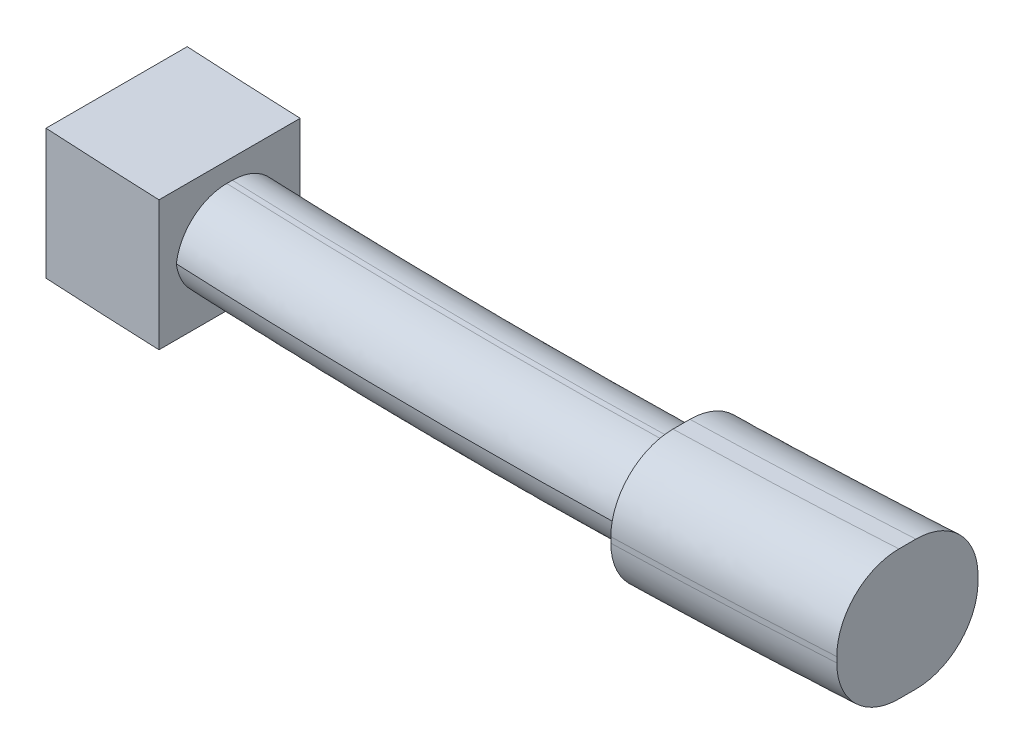
SolidWorks part; units mm, degrees
ref_plane "Front Plane" through (0, 0, 0) normal (0, 0, 1) x (1, 0, 0)
ref_plane "Top Plane" through (0, 0, 0) normal (0, 1, 0) x (1, 0, 0)
ref_plane "Right Plane" through (0, 0, 0) normal (1, 0, 0) x (0, 0, -1)
sketch "Sketch1" plane through (0, 0, 0) normal (0, 1, 0) x (1, 0, 0)
  line L1 (70, -12.5) -> (-70, -12.5)
  line L2 (70, -12.5) -> (70, 12.5)
  line L3 (70, 12.5) -> (-70, 12.5)
  line L4 (-70, -12.5) -> (-70, 12.5)
  line L5 (70, -12.5) -> (-70, 12.5) construction
  line L6 (70, 12.5) -> (-70, -12.5) construction
  point P0 (0, 0)
  point P5 (-70, 0)
  dimension "D1" = 140
  dimension "D2" = 25
extrude "Boss-Extrude1" add sketch "Sketch1" along normal blind 25
sketch "Sketch2" plane through (0, 0, 12.5) normal (0, 0, 1) x (1, 0, 0)
  line L0 (-70, 22.8376) -> (70, 22.8376)
  line L1 (-70, 25) -> (-70, 0) construction
  line L2 (70, 25) -> (70, 0) construction
  spline S0 degree 2 poles (-70, 12.5) (0, 10.0003) (70, 12.5) knots 0 0 0 1 1 1
  point P8 (-500000, 60752.5992)
sketch "Sketch3" plane through (-70, 0, 0) normal (-1, 0, 0) x (0, 0, 1)
  line L0 (12.5, 25) -> (-12.5, 0)
  line L1 (-12.5, 25) -> (12.5, 0)
  circle A0 centre (0, 12.5) radius 12.5
  point P10 (14.9425, 56.9827)
sketch "Sketch4" plane through (70, 0, 0) normal (1, 0, 0) x (0, 0, -1)
  line L0 (12.5, 25) -> (-12.5, 0)
  line L1 (-12.5, 25) -> (12.5, 0)
  circle A0 centre (0, 12.5) radius 12.4007
  point P10 (-7.4057, 0.9787)
sketch "Sketch5" plane through (0, 0, 12.5) normal (0, 0, 1) x (1, 0, 0)
  line L0 (30, 23.3673) -> (30, 19.8673)
  line L1 (-70, 25) -> (70, 25)
  line L2 (-50, 24.0204) -> (-50, 20.5204)
  line L3 (-70, 25) -> (70, 25) construction
  line L4 (-50, 20.5204) -> (-50, 1.0204)
  line L5 (30, 25) -> (-50, 25)
  line L6 (0, 11.2502) -> (0, 25)
  line L7 (-70, 21.5) -> (-50, 21.5)
  line L8 (0, 11.2502) -> (0, 14.7502)
  line L9 (-70, 25) -> (-70, 21.5)
  line L10 (-50, 1.0204) -> (-50, 4.813)
  line L11 (-70, 0) -> (-70, 2)
  line L12 (-70, 2) -> (-70, 0)
  line L13 (-70, 0) -> (70, 0)
  line L14 (70, 0) -> (70, 2)
  line L15 (0, 23) -> (0, 19.5)
  line L16 (30, 23.3673) -> (30, 0.3673)
  line L17 (30, 0.3673) -> (30, 3.8673)
  line L18 (0, 0) -> (0, 3.5)
  spline S0 degree 2 poles (-70, 25) (0, 21) (70, 25) knots 0 0 0 1 1 1
  spline S1 degree 2 poles (-70, 2) (0, -2) (70, 2) knots 0 0 0 1 1 1
  spline S2 degree 2 poles (-50, 20.5204) (-10.0053, 18.8878) (30, 19.8673) knots 0 0 0 1 1 1
  spline S3 degree 2 poles (-50, 4.813) (-10.0108, 2.8) (30, 3.8673) knots 0 0 0 1 1 1
  point P34 (0, 0)
  line M4 (-70, 0) -> (70, 0)
  line M5 (70, 0) -> (70, 25)
  line M6 (70, 25) -> (-70, 25)
  line M7 (-70, 25) -> (-70, 0)
  dimension "D1" = 3.5
  dimension "D2" = 3.5
  dimension "D3" = 3.5
  dimension "D4" = 3.5
  dimension "D5" = 3.5
  dimension "D6" = 3.5
  dimension "D7" = 3.5
  dimension "D8" = 3.5
extrude "Cut-Extrude1" cut sketch "Sketch5" against normal blind 25 contours S0 L6 L5 M6 | L6 S0 L1 M6 | L6 S2 L0 S0 | L2 S2 L6 S0 | S3 L4 S1 L18 | S3 L18 S1 L16 | S1 L13 M5 | S1 M7 M4 region at (15, 21.3725, 12.5) region at (26.25, 24.2, 12.5) region at (-26.25, 24.2, 12.5) region at (-25, 21.5901, 12.5) region at (15, 1.867, 12.5) region at (52.5, 0.6, 12.5) region at (-25.3372, 2.1562, 12.5) region at (-52.5, 0.6, 12.5)
sketch "Sketch6" plane through (0, 0, 12.5) normal (0, 0, 1) x (1, 0, 0)
  line L0 (30, 19.8673) -> (30, 3.8673)
  line L1 (-50, 20.5204) -> (-50, 4.813)
  line L2 (30, 3.8673) -> (30, 1.4859)
  line L3 (30, 1.4859) -> (-50, 1.4859)
  line L4 (-50, 4.813) -> (-50, 1.0204) construction
  line L5 (-50, 1.4859) -> (-50, 4.813)
  line L6 (-50, 20.5204) -> (30, 19.8673)
  line L7 (-50, 20.5204) -> (-50, 21.4699)
  line L8 (-50, 24.0204) -> (-50, 20.5204) construction
  line L10 (30, 23.3673) -> (30, 19.8673) construction
  line L11 (30, 20.9952) -> (30, 19.8673)
  line L13 (-50, 21.4699) -> (30, 21.4699)
  line L14 (-50, 21.4699) -> (-50, 1.4859)
  line L15 (-50, 1.4859) -> (30, 1.4859)
  line L16 (30, 21.4699) -> (30, 1.4859)
  line M8 (30, 23.3673) -> (30, 19.8673)
  spline M9 degree 2 poles (30, 19.8673) (-10.0053, 18.8878) (-50, 20.5204) knots 0 0 0 1 1 1
  line M10 (-50, 20.5204) -> (-50, 24.0204)
  line M14 (-50, 1.0204) -> (-50, 4.813)
  spline M15 degree 2 poles (-50, 4.813) (-10.0108, 2.8) (30, 3.8673) knots 0 0 0 1 1 1
  line M16 (30, 3.8673) -> (30, 0.3673)
extrude "Cut-Extrude13" cut sketch "Sketch6" against normal blind 3 contours L3 M16 M15 M14 | L1 L0 M9 M15 | L13 L6 M10 M8 | L6 M9 region at (-10.0011, 19.9327, 12.5) region at (-6.588, 20.818, 12.5) region at (-9.8776, 11.7909, 12.5) region at (-12.6928, 2.6835, 12.5)
sketch "Sketch9" plane through (0, 0, -12.5) normal (0, 0, -1) x (-1, 0, 0)
  line L0 (-30, 23.3673) -> (-30, 19.8673) construction
  line L1 (-30, 21.6173) -> (50, 21.6173)
  line L2 (-30, 21.6173) -> (-30, 2.9167)
  line L3 (-30, 2.9167) -> (50, 2.9167)
  line L4 (50, 21.6173) -> (50, 2.9167)
  line L5 (50, 4.813) -> (50, 1.0204) construction
extrude "Cut-Extrude14" cut sketch "Sketch9" against normal blind 3
fillet "Fillet1" radius 11 4 edges
fillet "Fillet5" radius 9 4 edges
